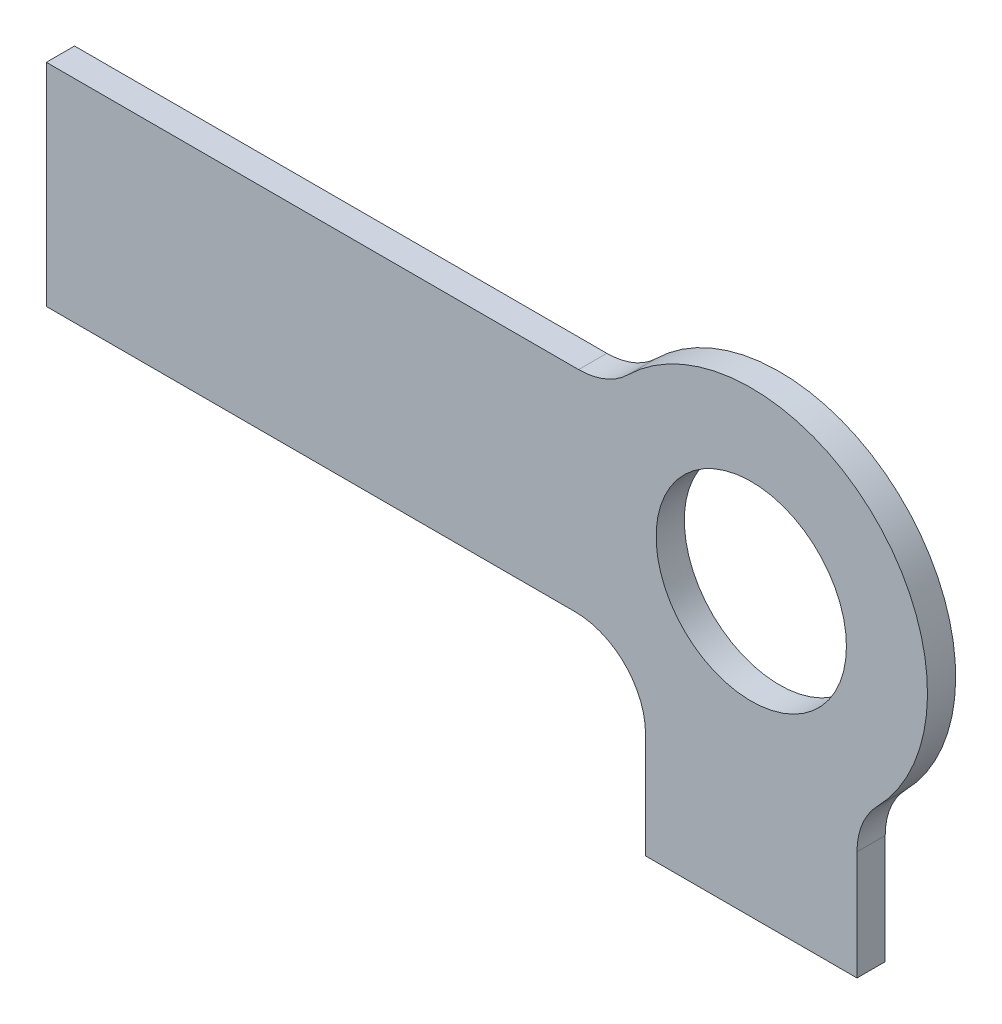
SolidWorks part; units mm, degrees
ref_plane "Front" through (0, 0, 0) normal (0, 0, 1) x (1, 0, 0)
ref_plane "Top" through (0, 0, 0) normal (0, 1, 0) x (1, 0, 0)
ref_plane "Right" through (0, 0, 0) normal (1, 0, 0) x (0, 0, -1)
sketch "Sketch1" plane through (0, 0, 0) normal (0, 0, 1) x (1, 0, 0)
  line L0 (-10, 1.5) -> (-2.4495, 1.5)
  line L1 (-10, -1.5) -> (-2.5, -1.5)
  line L2 (-1.5, -2.5) -> (-1.5, -4)
  line L3 (1.5, -4) -> (1.5, -2.4495)
  line L4 (-10, 1.5) -> (-10, -1.5)
  line L5 (-1.5, -4) -> (1.5, -4)
  circle A1 centre (0, 0) radius 1.35
  arc A2 (-2.4495, 1.5) -> (-1.7496, 1.7857) centre (-2.4495, 2.5) ccw
  arc A3 (-1.5, -2.5) -> (-2.5, -1.5) centre (-2.5, -2.5) ccw
  arc A4 (1.7857, -1.7496) -> (1.5, -2.4495) centre (2.5, -2.4495) ccw
  arc A5 (1.7857, -1.7496) -> (-1.7496, 1.7857) centre (0, 0) ccw
  dimension "D4" = 3
  dimension "D5" = 1.5
  dimension "D6" = 1.5
extrude "Base-Extrude" add sketch "Sketch1" against normal blind 0.4
equation "\"D5@Sketch1\" = \"B@Sketch1\" / 2"
equation "\"D4@Sketch1\" = \"B@Sketch1\""
equation "\"D6@Sketch1\" = \"B@Sketch1\" / 2"
